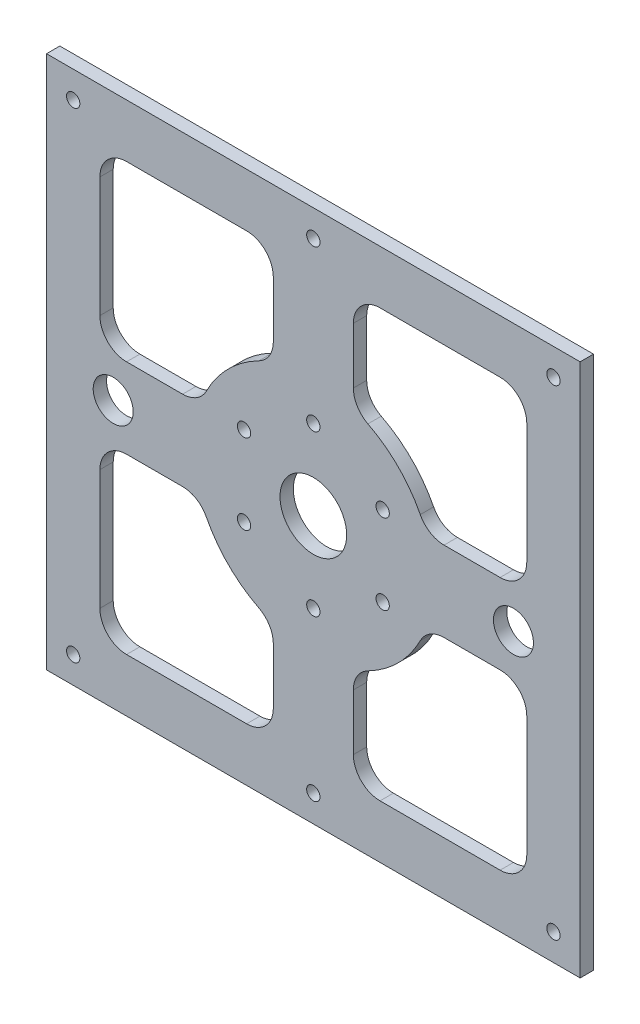
SolidWorks part; units mm, degrees
ref_plane "正面" through (0, 0, 0) normal (0, 0, 1) x (1, 0, 0)
ref_plane "平面" through (0, 0, 0) normal (0, 1, 0) x (1, 0, 0)
ref_plane "右側面" through (0, 0, 0) normal (1, 0, 0) x (0, 0, -1)
sketch "ｽｹｯﾁ1" plane through (0, 0, 0) normal (0, 0, 1) x (1, 0, 0)
  line L1 (-100, 100) -> (100, 100)
  line L2 (-100, 100) -> (-100, -100)
  line L3 (-100, -100) -> (100, -100)
  line L4 (100, 100) -> (100, -100)
  line L5 (-100, 100) -> (100, -100) construction
  line L6 (-100, -100) -> (100, 100) construction
  circle A0 centre (0, 0) radius 12.5
  point P0 (0, 0)
  dimension "D3" = 25
  dimension "D1" = 200
  dimension "D2" = 200
extrude "ﾎﾞｽ - 押し出し1" add sketch "ｽｹｯﾁ1" along normal blind 5
sketch "ｽｹｯﾁ3" plane through (0, 0, 5) normal (0, 0, 1) x (1, 0, 0)
  line L0 (100, 100) -> (-100, 100) construction
  line L1 (-90, 90) -> (90, 90) construction
  line L2 (-90, 90) -> (-90, -90) construction
  line L3 (-90, -90) -> (90, -90) construction
  line L4 (90, 90) -> (90, -90) construction
  line L5 (-90, 90) -> (90, -90) construction
  line L6 (-90, -90) -> (90, 90) construction
  line L7 (-100, 100) -> (-100, -100) construction
  circle A0 centre (0, 90) radius 2.5
  circle A1 centre (90, 90) radius 2.5
  circle A2 centre (-90, 90) radius 2.5
  circle A3 centre (-90, -90) radius 2.5
  circle A4 centre (0, -90) radius 2.5
  circle A5 centre (90, -90) radius 2.5
  point P0 (0, 0)
  dimension "D3" = 5
  dimension "D1" = 10
  dimension "D2" = 10
extrude "ｶｯﾄ - 押し出し2" cut sketch "ｽｹｯﾁ3" against normal through all
sketch "ｽｹｯﾁ4" plane through (0, 0, 5) normal (0, 0, 1) x (1, 0, 0)
  line L0 (0, 30) -> (0, 0) construction
  line L1 (-25.9808, -15) -> (0, 0) construction
  line L2 (0, 0) -> (25.9808, -15) construction
  line L3 (0, 0) -> (-75, 0) construction
  circle A0 centre (0, 30) radius 2.5
  circle A1 centre (25.9808, 15) radius 2.5
  circle A2 centre (25.9808, -15) radius 2.5
  circle A3 centre (0, -30) radius 2.5
  circle A4 centre (-25.9808, -15) radius 2.5
  circle A5 centre (-25.9808, 15) radius 2.5
  circle A6 centre (-75, 0) radius 7.5
  circle A7 centre (75, 0) radius 7.5
  dimension "D1" = 5
  dimension "D4" = 15
  dimension "D2" = 30
  dimension "D5" = 75
  dimension "D3" = 6
extrude "ｶｯﾄ - 押し出し3" cut sketch "ｽｹｯﾁ4" against normal through all
sketch "ｽｹｯﾁ5" plane through (0, 0, 5) normal (0, 0, 1) x (1, 0, 0)
  line L0 (-80, 70) -> (-80, 25)
  line L1 (-70, 15) -> (-48.9898, 15)
  line L4 (-15, 48.9898) -> (-15, 70)
  line L5 (-25, 80) -> (-70, 80)
  line L6 (-100, 100) -> (-100, -100) construction
  line L7 (100, 100) -> (-100, 100) construction
  line L8 (-100, 0) -> (0, 0) construction
  line L9 (0, 0) -> (0, 100) construction
  line L10 (15, 48.9898) -> (15, 70)
  line L11 (25, 80) -> (70, 80)
  line L12 (80, 70) -> (80, 25)
  line L13 (70, 15) -> (48.9898, 15)
  line L14 (15, -48.9898) -> (15, -70)
  line L15 (70, -15) -> (48.9898, -15)
  line L16 (80, -70) -> (80, -25)
  line L17 (25, -80) -> (70, -80)
  line L18 (-15, -48.9898) -> (-15, -70)
  line L19 (-25, -80) -> (-70, -80)
  line L20 (-80, -70) -> (-80, -25)
  line L21 (-70, -15) -> (-48.9898, -15)
  arc A0 (-20.4545, 40.0826) -> (-40.0826, 20.4545) centre (0, 0) ccw
  arc A1 (-80, 25) -> (-70, 15) centre (-70, 25) ccw
  arc A2 (-48.9898, 15) -> (-40.0826, 20.4545) centre (-48.9898, 25) ccw
  arc A3 (-20.4545, 40.0826) -> (-15, 48.9898) centre (-25, 48.9898) ccw
  arc A4 (-15, 70) -> (-25, 80) centre (-25, 70) ccw
  arc A5 (-80, 70) -> (-70, 80) centre (-70, 70) cw
  arc A6 (15, 70) -> (25, 80) centre (25, 70) cw
  arc A7 (80, 70) -> (70, 80) centre (70, 70) ccw
  arc A8 (80, 25) -> (70, 15) centre (70, 25) cw
  arc A9 (48.9898, 15) -> (40.0826, 20.4545) centre (48.9898, 25) cw
  arc A10 (20.4545, 40.0826) -> (15, 48.9898) centre (25, 48.9898) cw
  arc A11 (20.4545, 40.0826) -> (40.0826, 20.4545) centre (0, 0) cw
  arc A12 (20.4545, -40.0826) -> (15, -48.9898) centre (25, -48.9898) ccw
  arc A13 (20.4545, -40.0826) -> (40.0826, -20.4545) centre (0, 0) ccw
  arc A14 (48.9898, -15) -> (40.0826, -20.4545) centre (48.9898, -25) ccw
  arc A15 (80, -25) -> (70, -15) centre (70, -25) ccw
  arc A16 (80, -70) -> (70, -80) centre (70, -70) cw
  arc A17 (15, -70) -> (25, -80) centre (25, -70) ccw
  arc A18 (-15, -70) -> (-25, -80) centre (-25, -70) cw
  arc A19 (-80, -70) -> (-70, -80) centre (-70, -70) ccw
  arc A20 (-80, -25) -> (-70, -15) centre (-70, -25) cw
  arc A21 (-48.9898, -15) -> (-40.0826, -20.4545) centre (-48.9898, -25) cw
  arc A22 (-20.4545, -40.0826) -> (-15, -48.9898) centre (-25, -48.9898) cw
  arc A23 (-20.4545, -40.0826) -> (-40.0826, -20.4545) centre (0, 0) cw
  dimension "D1" = 90
  dimension "D6" = 10
  dimension "D2" = 20
  dimension "D3" = 20
  dimension "D4" = 15
  dimension "D5" = 15
extrude "ｶｯﾄ - 押し出し4" cut sketch "ｽｹｯﾁ5" against normal through all
